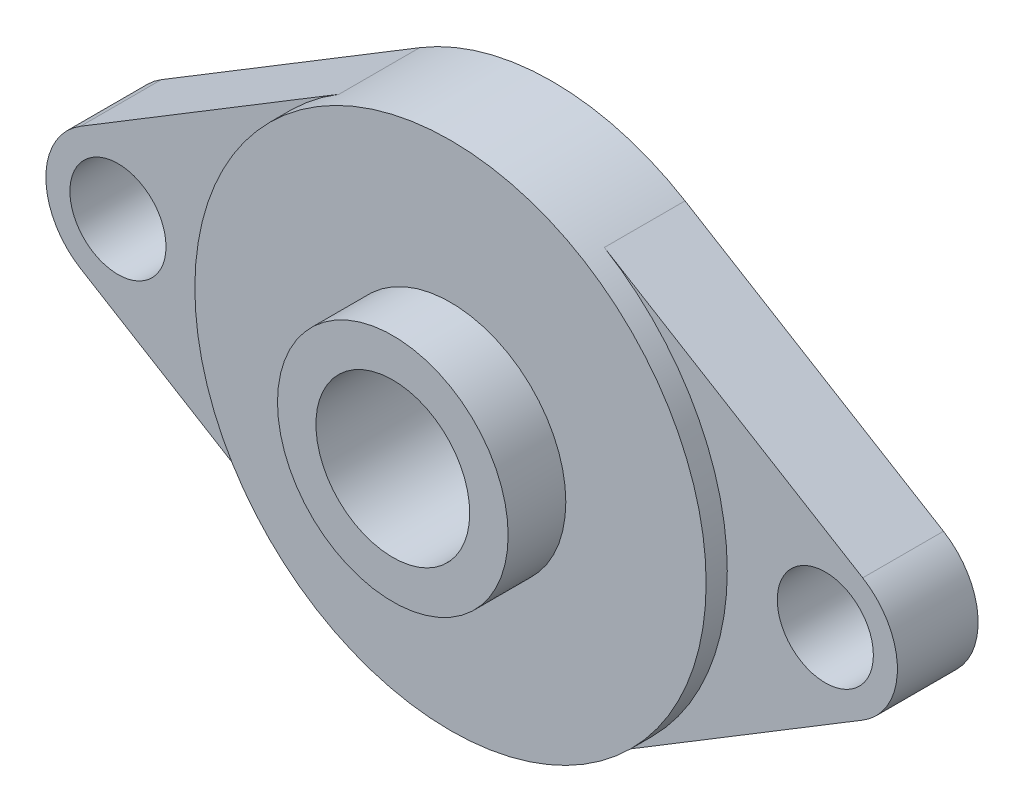
SolidWorks part; units mm, degrees
ref_plane "前视基准面" through (0, 0, 0) normal (0, 0, 1) x (1, 0, 0)
ref_plane "上视基准面" through (0, 0, 0) normal (0, 1, 0) x (1, 0, 0)
ref_plane "右视基准面" through (0, 0, 0) normal (1, 0, 0) x (0, 0, -1)
sketch "草图1" plane through (0, 0, 0) normal (0, 0, 1) x (1, 0, 0)
  line L0 (0, 13.6354) -> (0, 0) construction
  line L1 (0, 0) -> (18.4, 0) construction
  line L2 (6.903, 11.3683) -> (20.3463, 3.2054)
  line L3 (6.903, -11.3683) -> (20.3463, -3.2054)
  line L4 (-6.903, -11.3683) -> (-20.3463, -3.2054)
  line L5 (-6.903, 11.3683) -> (-20.3463, 3.2054)
  circle A0 centre (0, 0) radius 4
  circle A1 centre (0, 0) radius 13.3
  circle A2 centre (18.4, 0) radius 2.5
  circle A3 centre (18.4, 0) radius 3.75
  circle A4 centre (-18.4, 0) radius 3.75
  circle A5 centre (-18.4, 0) radius 2.5
  dimension "D1" = 8
  dimension "D2" = 5
  dimension "D3" = 7.5
  dimension "D4" = 26.6
  dimension "D5" = 18.4
extrude "凸台-拉伸1" add sketch "草图1" along normal blind 4.2 contours A4 A5 | L5 A4 L4 A1 | A1 A0 | A3 L2 A1 L3 | A3 A2 region at (14.0805, 0, 0) region at (11.2631, 6.3378, 0) region at (21.5757, 1.787, 0) region at (-14.0805, 0, 0) region at (-16.613, 3.1757, 0)
extrude "凸台-拉伸2" add sketch "草图1<3>" along normal blind 8.3 contours A1 A0 region at (11.2631, 6.3378, 0)
sketch "草图1<3>" plane through (0, 0, 0) normal (0, 0, 1) x (1, 0, 0) same geometry as "草图1"
sketch "草图2" plane through (0, 0, 8.3) normal (0, 0, 1) x (1, 0, 0)
  circle A0 centre (0, 0) radius 13.3 construction
  circle A1 centre (0, 0) radius 13.3
  circle A2 centre (0, 0) radius 4 construction
  circle A3 centre (0, 0) radius 4 construction
  circle A4 centre (0, 0) radius 6
  dimension "D1" = 2
extrude "切除-拉伸1" cut sketch "草图2" against normal blind 3
